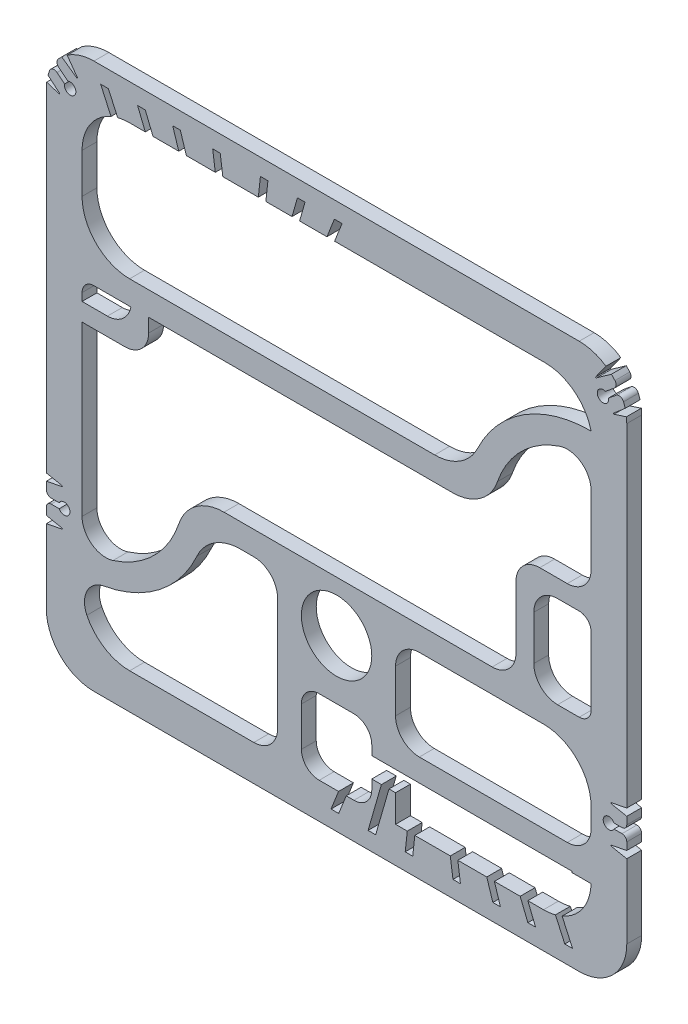
SolidWorks part; units mm, degrees
ref_plane "Front Plane" through (0, 0, 0) normal (0, 0, 1) x (1, 0, 0)
ref_plane "Top Plane" through (0, 0, 0) normal (0, 1, 0) x (1, 0, 0)
ref_plane "Right Plane" through (0, 0, 0) normal (1, 0, 0) x (0, 0, -1)
sketch "Sketch1" plane through (0, 0, 0) normal (0, 0, 1) x (1, 0, 0)
  line L0 (44.642, 21.8842) -> (44.642, 18.0742) construction
  line L1 (-10.1934, 21.8842) -> (51.7832, 21.8842)
  line L2 (-10.1934, 21.8842) -> (-10.1934, -36.406)
  line L3 (-10.1934, -36.406) -> (51.7832, -36.406)
  line L4 (51.7832, 21.8842) -> (51.7832, -36.406)
  line L5 (47.9732, -32.596) -> (-6.3834, -32.596)
  line L6 (47.9732, -32.596) -> (47.9732, 18.0742)
  line L7 (47.9732, 18.0742) -> (-6.3834, 18.0742)
  line L8 (-6.3834, -32.596) -> (-6.3834, 18.0742)
  line L9 (44.642, 19.9792) -> (-35.1587, 19.9792) construction
  line L10 (-6.3834, -31.0517) -> (-10.1934, -31.0517) construction
  line L11 (-8.2884, -31.0517) -> (-8.2884, 6.9585) construction
  line L12 (20.6521, 19.9792) -> (21.1982, 19.9792) construction
  line L14 (3.0779, -32.596) -> (3.0779, -36.406) construction
  line L15 (3.0779, -34.501) -> (37.3423, -34.501) construction
  line L16 (47.9732, -15.6937) -> (47.9732, 12.9942) construction
  line L17 (51.7832, 15.2205) -> (47.9732, 15.2205) construction
  line L18 (49.8782, 15.2205) -> (49.8782, -0.9437) construction
  line L20 (20.9378, -34.501) -> (20.3916, -34.501) construction
  line L21 (-6.3834, 8.0412) -> (-6.3834, -15.6937) construction
  dimension "D1" = 3.81
  dimension "D2" = 3.81
extrude "Boss-Extrude1" add sketch "Sketch1" along normal blind 1.5875
sketch "Sketch2" plane through (0, 0, 0) normal (0, 0, -1) x (-1, 0, 0)
  line L0 (-47.9732, -32.596) -> (-47.9732, 18.0742) construction
  line L1 (-34.8696, 3.653) -> (6.3834, 3.653)
  line L2 (-47.9732, 3.653) -> (-47.9732, 0.8076)
  line L3 (-37.4096, 1.113) -> (6.3834, 1.113)
  line L4 (6.3834, 3.653) -> (6.3834, 1.113)
  line L5 (6.3834, 18.0742) -> (6.3834, -32.596) construction
  line L6 (-33.4496, 1.113) -> (-36.4496, 1.113) construction
  line L7 (1.2504, -12.887) -> (-36.4496, -12.887) construction
  line L8 (-47.9732, -15.427) -> (-6.8239, -15.427)
  line L9 (-47.9732, -15.427) -> (-47.9732, -12.887)
  line L10 (-47.9732, -12.887) -> (-4.5259, -12.887)
  line L11 (1.357, -21.2563) -> (14.2432, -21.2563) construction
  line L12 (6.3834, -23.7963) -> (6.3834, -26.3363)
  line L13 (-47.9732, 14.2166) -> (-47.9732, 11.6766)
  arc A0 (-47.9732, 11.6766) -> (-37.4096, 1.113) centre (-47.9732, 1.113) cw
  arc A1 (-47.9732, 14.2166) -> (-34.8696, 3.653) centre (-47.9732, 0.8076) cw
  arc A2 (6.3834, -23.7963) -> (-4.5259, -12.887) centre (6.3834, -12.887) cw
  arc A3 (-6.8239, -15.427) -> (6.3834, -26.3363) centre (6.3834, -12.887) ccw
  circle A5 centre (1.357, -18.2591) radius 2.9972 construction
  line M5 (-47.9732, -32.596) -> (-47.9732, 18.0742)
  line M7 (6.3834, 18.0742) -> (6.3834, -32.596)
  dimension "D5" = 2.54
  dimension "D1" = 2.54
  dimension "D2" = 2.54
  dimension "D3" = 2.54
  dimension "D4" = 2.54
  dimension "D6" = 2.54
  dimension "D7" = 2.54
extrude "Boss-Extrude2" add sketch "Sketch2" against normal up to surface (1.5875 mm away) contours A1 A0 L3 L1 M5 M7 | L10 L8 M5 M7 region at (14.2431, 3.0939, 0) region at (-5.8234, -25.0663, 0) up to face at (20.7949, -7.2609, 1.5875)
sketch "Sketch3" plane through (0, 0, 0) normal (0, 0, -1) x (-1, 0, 0)
  line L0 (-47.9732, -1.1649) -> (-39.9496, -1.1649)
  line L1 (-47.9732, -12.887) -> (-47.9732, 11.6766) construction
  line L2 (-39.9496, -4.387) -> (-39.9496, -11.387) construction
  line L3 (-39.9496, -1.1649) -> (-39.9496, -12.887)
  line L4 (-47.9732, -12.887) -> (-4.5259, -12.887) construction
  line L5 (-39.9496, -12.887) -> (-41.8546, -12.887)
  line L6 (-41.8546, -12.887) -> (-41.8546, -3.0699)
  line L7 (-41.8546, -3.0699) -> (-47.9732, -3.0699)
  line L8 (-47.9732, -3.0699) -> (-47.9732, -1.1649)
  line L9 (-42.9468, 0.7401) -> (-53.4831, 0.7401) construction
  line L10 (-0.7296, 1.113) -> (-0.7296, -2.887)
  line L11 (-37.4096, 1.113) -> (6.3834, 1.113) construction
  line L12 (-1.9996, -2.887) -> (1.2504, -2.887) construction
  line L13 (-0.7296, -2.887) -> (6.3834, -2.887)
  line L14 (6.3834, 1.113) -> (6.3834, -23.7963) construction
  line L15 (6.3834, -2.887) -> (6.3834, -0.982)
  line L16 (6.3834, -0.982) -> (1.1754, -0.982)
  line L17 (1.1754, -0.982) -> (1.1754, 1.113)
  line L18 (1.1754, 1.113) -> (-0.7296, 1.113)
  circle A0 centre (-42.9468, 3.7373) radius 2.9972 construction
  dimension "D1" = 1.905
  dimension "D2" = 1.905
  dimension "D3" = 1.905
  dimension "D4" = 1.905
  dimension "D5" = 1.27
  dimension "D6" = 1.905
extrude "Boss-Extrude3" add sketch "Sketch3" against normal up to surface (1.5875 mm away) up to face at (20.8645, -5.9566, 1.5875)
fillet "Fillet1" radius 5.08 4 edges at (51.7832, -36.406, 0.7937) (-10.1934, -36.406, 0.7937) (-10.1934, 21.8842, 0.7937) (51.7832, 21.8842, 0.7937)
fillet "Fillet2" radius 5.08 10 edges at (6.8239, -15.427, 0.7937) (47.9732, -15.427, 0.7937) (47.9732, -32.596, 0.7937) (-6.3834, -32.596, 0.7937) (34.8696, 3.653, 0.7938) (-6.3834, 3.653, 0.7937) (47.9732, 18.0742, 0.7937) (-6.3834, 18.0742, 0.7937) (4.5259, -12.887, 0.7937) (37.4096, 1.113, 0.7938)
fillet "Fillet3" radius 2.54 10 edges at (41.8546, -3.0699, 0.7938) (39.9496, -12.887, 0.7938) (41.8546, -12.887, 0.7938) (39.9496, -1.1649, 0.7938) (47.9732, -1.1649, 0.7938) (-1.1754, -0.982, 0.7938) (0.7296, -2.887, 0.7938) (47.9732, 11.6766, 0.7937) (-6.3834, -26.3363, 0.7937) (-6.3834, -23.7963, 0.7937)
fillet "Fillet4" radius 1.27 3 edges at (47.9732, -12.887, 0.7937) (47.9732, -3.0699, 0.7938) (-6.3834, 1.113, 0.7938)
sketch "Sketch5" plane through (0, 0, 0) normal (0, 0, -1) x (-1, 0, 0)
  line L0 (-42.8932, -15.427) -> (-10.5066, -15.427) construction
  line L1 (-27.0941, -15.427) -> (-14.4957, -15.427)
  line L2 (-27.0941, -15.427) -> (-27.0941, -32.596)
  line L3 (-27.0941, -32.596) -> (-14.4957, -32.596)
  line L4 (-14.4957, -15.427) -> (-14.4957, -32.596)
  line L5 (1.3034, -32.596) -> (-42.8932, -32.596) construction
  line L6 (-24.5541, -18.2972) -> (-27.0941, -18.2972) construction
  line L9 (-17.0357, -18.2972) -> (-14.4957, -18.2972) construction
  circle A1 centre (-20.7949, -18.2972) radius 3.7592 construction
  dimension "D1" = 2.54
extrude "Boss-Extrude4" add sketch "Sketch5" against normal up to surface (1.5875 mm away) up to face at (-4.5227, -0.0173, 1.5875)
sketch "Sketch6" plane through (0, 0, 0) normal (0, 0, -1) x (-1, 0, 0)
  circle A0 centre (-20.7949, -18.2972) radius 3.7592 construction
  circle A1 centre (-20.7949, -18.2972) radius 3.7592
extrude "Cut-Extrude2" cut sketch "Sketch6" against normal up to surface (1.5875 mm away) up to face at (4.768, -24.4396, 1.5875)
sketch "Sketch7" plane through (0, 0, 0) normal (0, 0, -1) x (-1, 0, 0)
  line L0 (-27.0941, -15.427) -> (-27.0941, -32.596) construction
  line L1 (-24.5541, -24.5964) -> (-17.0357, -24.5964)
  line L2 (-24.5541, -24.5964) -> (-24.5541, -32.596)
  line L3 (-24.5541, -32.596) -> (-17.0357, -32.596)
  line L4 (-17.0357, -24.5964) -> (-17.0357, -32.596)
  line L5 (-14.4957, -32.596) -> (-14.4957, -15.427) construction
  line L6 (1.3034, -32.596) -> (-14.4957, -32.596) construction
  line L7 (-20.7949, -22.0564) -> (-6.5424, -22.0564) construction
  line L8 (-20.7949, -22.0564) -> (-20.7949, -21.3452) construction
  circle A0 centre (-20.7949, -18.2972) radius 3.7592 construction
  dimension "D1" = 2.54
  dimension "D2" = 2.54
  dimension "D3" = 2.54
extrude "Cut-Extrude3" cut sketch "Sketch7" against normal up to surface (1.5875 mm away) up to face at (24.5541, -18.2972, 1.5875)
fillet "Fillet5" radius 1.905 4 edges at (24.5541, -32.596, 0.7937) (17.0357, -32.596, 0.7938) (17.0357, -24.5964, 0.7938) (24.5541, -24.5964, 0.7938)
sketch "Sketch8" plane through (0, 0, 0) normal (0, 0, -1) x (-1, 0, 0)
  line L0 (-47.9732, -27.516) -> (-47.9732, -20.507) construction
  line L1 (-47.9732, -25.103) -> (-27.0941, -25.103)
  line L2 (-47.9732, -25.103) -> (-47.9732, -27.643)
  line L3 (-47.9732, -27.643) -> (-27.0941, -27.643)
  line L4 (-27.0941, -25.103) -> (-27.0941, -27.643)
  line L5 (-27.0941, -15.427) -> (-27.0941, -32.596) construction
  line L6 (-45.7916, -27.643) -> (-20.3916, -27.643) construction
  dimension "D1" = 2.54
extrude "Boss-Extrude5" add sketch "Sketch8" against normal up to surface (1.5875 mm away) up to face at (20.7949, -28.5962, 1.5875)
fillet "Fillet6" radius 2.54 5 edges at (27.0941, -15.427, 0.7937) (14.4957, -15.427, 0.7937) (14.4957, -32.596, 0.7937) (27.0941, -25.103, 0.7937) (47.9732, -25.103, 0.7937)
sketch "Sketch4" plane through (0, 0, 0) normal (0, 0, -1) x (-1, 0, 0)
  line L0 (3.2504, -2.887) -> (4.7504, -4.387) construction
  line L1 (4.7504, -11.387) -> (3.2504, -12.887) construction
  line L2 (3.2504, -2.887) -> (4.7504, -4.387)
  line L3 (4.7504, -11.387) -> (3.2504, -12.887)
  line L4 (4.7504, -4.387) -> (4.7504, -11.387) construction
  line L5 (4.7504, -4.387) -> (4.7504, -11.387)
  line L6 (3.2504, -2.887) -> (3.2504, -12.887)
  line L32 (4.2018, 13.1212) -> (4.2018, 15.0262)
  line L33 (4.2018, 15.0262) -> (1.9539, 15.0262)
  line L34 (1.9539, 15.0262) -> (4.2018, 19.9792)
  line L35 (4.2018, 19.9792) -> (3.6556, 19.9792)
  line L36 (3.6556, 19.9792) -> (1.4078, 15.0262)
  line L37 (1.4078, 15.0262) -> (-1.7417, 15.0262)
  line L38 (-1.7417, 15.0262) -> (0.2648, 19.9792)
  line L39 (0.2648, 19.9792) -> (-0.2814, 19.9792)
  line L40 (-0.2814, 19.9792) -> (-2.2879, 15.0262)
  line L41 (-2.2879, 15.0262) -> (-5.0437, 15.0262)
  line L42 (-5.0437, 15.0262) -> (-3.469, 19.9792)
  line L43 (-3.469, 19.9792) -> (-4.0152, 19.9792)
  line L44 (-4.0152, 19.9792) -> (-5.5899, 15.0262)
  line L45 (-5.5899, 15.0262) -> (-8.3965, 15.0262)
  line L46 (-8.3965, 15.0262) -> (-7.7108, 19.9792)
  line L47 (-7.7108, 19.9792) -> (-8.257, 19.9792)
  line L48 (-8.257, 19.9792) -> (-8.9427, 15.0262)
  line L49 (-8.9427, 15.0262) -> (-12.2319, 15.0262)
  line L50 (-12.2319, 15.0262) -> (-12.7781, 19.9792)
  line L51 (-12.7781, 19.9792) -> (-13.3242, 19.9792)
  line L52 (-13.3242, 19.9792) -> (-12.7781, 15.0262)
  line L53 (-12.7781, 15.0262) -> (-15.2926, 15.0262)
  line L54 (-15.2926, 15.0262) -> (-16.7151, 19.9792)
  line L55 (-16.7151, 19.9792) -> (-17.2612, 19.9792)
  line L56 (-17.2612, 19.9792) -> (-15.8388, 15.0262)
  line L57 (-15.8388, 15.0262) -> (-18.6963, 15.0262)
  line L58 (-18.6963, 15.0262) -> (-20.6521, 19.9792)
  line L59 (-20.6521, 19.9792) -> (-21.1982, 19.9792)
  line L60 (-21.1982, 19.9792) -> (-19.2425, 15.0262)
  line L61 (-19.2425, 15.0262) -> (-21.1982, 15.0262)
  line L62 (-21.1982, 15.0262) -> (-21.1982, 13.1212)
  line L63 (-21.1982, 13.1212) -> (4.2018, 13.1212)
  line L64 (4.2018, 13.1212) -> (4.2018, 15.0262) construction
  line L65 (4.2018, 15.0262) -> (1.9539, 15.0262) construction
  line L66 (1.9539, 15.0262) -> (4.2018, 19.9792) construction
  line L67 (4.2018, 19.9792) -> (3.6556, 19.9792) construction
  line L68 (3.6556, 19.9792) -> (1.4078, 15.0262) construction
  line L69 (1.4078, 15.0262) -> (-1.7417, 15.0262) construction
  line L70 (-1.7417, 15.0262) -> (0.2648, 19.9792) construction
  line L71 (0.2648, 19.9792) -> (-0.2814, 19.9792) construction
  line L72 (-0.2814, 19.9792) -> (-2.2879, 15.0262) construction
  line L73 (-2.2879, 15.0262) -> (-5.0437, 15.0262) construction
  line L74 (-5.0437, 15.0262) -> (-3.469, 19.9792) construction
  line L75 (-3.469, 19.9792) -> (-4.0152, 19.9792) construction
  line L76 (-4.0152, 19.9792) -> (-5.5899, 15.0262) construction
  line L77 (-5.5899, 15.0262) -> (-8.3965, 15.0262) construction
  line L78 (-8.3965, 15.0262) -> (-7.7108, 19.9792) construction
  line L79 (-7.7108, 19.9792) -> (-8.257, 19.9792) construction
  line L80 (-8.257, 19.9792) -> (-8.9427, 15.0262) construction
  line L81 (-8.9427, 15.0262) -> (-12.2319, 15.0262) construction
  line L82 (-12.2319, 15.0262) -> (-12.7781, 19.9792) construction
  line L83 (-12.7781, 19.9792) -> (-13.3242, 19.9792) construction
  line L84 (-13.3242, 19.9792) -> (-12.7781, 15.0262) construction
  line L85 (-12.7781, 15.0262) -> (-15.2926, 15.0262) construction
  line L86 (-15.2926, 15.0262) -> (-16.7151, 19.9792) construction
  line L87 (-16.7151, 19.9792) -> (-17.2612, 19.9792) construction
  line L88 (-17.2612, 19.9792) -> (-15.8388, 15.0262) construction
  line L89 (-15.8388, 15.0262) -> (-18.6963, 15.0262) construction
  line L90 (-18.6963, 15.0262) -> (-20.6521, 19.9792) construction
  line L91 (-20.6521, 19.9792) -> (-21.1982, 19.9792) construction
  line L92 (-21.1982, 19.9792) -> (-19.2425, 15.0262) construction
  line L93 (-19.2425, 15.0262) -> (-21.1982, 15.0262) construction
  line L94 (-21.1982, 15.0262) -> (-21.1982, 13.1212) construction
  line L95 (-21.1982, 13.1212) -> (4.2018, 13.1212) construction
  line L96 (-45.7916, -27.643) -> (-45.7916, -29.548)
  line L97 (-45.7916, -29.548) -> (-43.5438, -29.548)
  line L98 (-43.5438, -29.548) -> (-45.7916, -34.501)
  line L99 (-45.7916, -34.501) -> (-45.2455, -34.501)
  line L100 (-45.2455, -34.501) -> (-42.9976, -29.548)
  line L101 (-42.9976, -29.548) -> (-39.8482, -29.548)
  line L102 (-39.8482, -29.548) -> (-41.8546, -34.501)
  line L103 (-41.8546, -34.501) -> (-41.3085, -34.501)
  line L104 (-41.3085, -34.501) -> (-39.302, -29.548)
  line L105 (-39.302, -29.548) -> (-36.5462, -29.548)
  line L106 (-36.5462, -29.548) -> (-38.1208, -34.501)
  line L107 (-38.1208, -34.501) -> (-37.5747, -34.501)
  line L108 (-37.5747, -34.501) -> (-36, -29.548)
  line L109 (-36, -29.548) -> (-33.1934, -29.548)
  line L110 (-33.1934, -29.548) -> (-33.879, -34.501)
  line L111 (-33.879, -34.501) -> (-33.3329, -34.501)
  line L112 (-33.3329, -34.501) -> (-32.6472, -29.548)
  line L113 (-32.6472, -29.548) -> (-29.358, -29.548)
  line L114 (-29.358, -29.548) -> (-28.8118, -34.501)
  line L115 (-28.8118, -34.501) -> (-28.2656, -34.501)
  line L116 (-28.2656, -34.501) -> (-28.8118, -29.548)
  line L117 (-28.8118, -29.548) -> (-26.2973, -29.548)
  line L118 (-26.2973, -29.548) -> (-24.8748, -34.501)
  line L119 (-24.8748, -34.501) -> (-24.3286, -34.501)
  line L120 (-24.3286, -34.501) -> (-25.7511, -29.548)
  line L121 (-25.7511, -29.548) -> (-22.8935, -29.548)
  line L122 (-22.8935, -29.548) -> (-20.9378, -34.501)
  line L123 (-20.9378, -34.501) -> (-20.3916, -34.501)
  line L124 (-20.3916, -34.501) -> (-22.3474, -29.548)
  line L125 (-22.3474, -29.548) -> (-20.3916, -29.548)
  line L126 (-20.3916, -29.548) -> (-20.3916, -27.643)
  line L127 (-20.3916, -27.643) -> (-45.7916, -27.643)
  line L128 (-45.7916, -27.643) -> (-45.7916, -29.548) construction
  line L129 (-45.7916, -29.548) -> (-43.5438, -29.548) construction
  line L130 (-43.5438, -29.548) -> (-45.7916, -34.501) construction
  line L131 (-45.7916, -34.501) -> (-45.2455, -34.501) construction
  line L132 (-45.2455, -34.501) -> (-42.9976, -29.548) construction
  line L133 (-42.9976, -29.548) -> (-39.8482, -29.548) construction
  line L134 (-39.8482, -29.548) -> (-41.8546, -34.501) construction
  line L135 (-41.8546, -34.501) -> (-41.3085, -34.501) construction
  line L136 (-41.3085, -34.501) -> (-39.302, -29.548) construction
  line L137 (-39.302, -29.548) -> (-36.5462, -29.548) construction
  line L138 (-36.5462, -29.548) -> (-38.1208, -34.501) construction
  line L139 (-38.1208, -34.501) -> (-37.5747, -34.501) construction
  line L140 (-37.5747, -34.501) -> (-36, -29.548) construction
  line L141 (-36, -29.548) -> (-33.1934, -29.548) construction
  line L142 (-33.1934, -29.548) -> (-33.879, -34.501) construction
  line L143 (-33.879, -34.501) -> (-33.3329, -34.501) construction
  line L144 (-33.3329, -34.501) -> (-32.6472, -29.548) construction
  line L145 (-32.6472, -29.548) -> (-29.358, -29.548) construction
  line L146 (-29.358, -29.548) -> (-28.8118, -34.501) construction
  line L147 (-28.8118, -34.501) -> (-28.2656, -34.501) construction
  line L148 (-28.2656, -34.501) -> (-28.8118, -29.548) construction
  line L149 (-28.8118, -29.548) -> (-26.2973, -29.548) construction
  line L150 (-26.2973, -29.548) -> (-24.8748, -34.501) construction
  line L151 (-24.8748, -34.501) -> (-24.3286, -34.501) construction
  line L152 (-24.3286, -34.501) -> (-25.7511, -29.548) construction
  line L153 (-25.7511, -29.548) -> (-22.8935, -29.548) construction
  line L154 (-22.8935, -29.548) -> (-20.9378, -34.501) construction
  line L155 (-20.9378, -34.501) -> (-20.3916, -34.501) construction
  line L156 (-20.3916, -34.501) -> (-22.3474, -29.548) construction
  line L157 (-22.3474, -29.548) -> (-20.3916, -29.548) construction
  line L158 (-20.3916, -29.548) -> (-20.3916, -27.643) construction
  line L159 (-20.3916, -27.643) -> (-45.7916, -27.643) construction
  line L263 (4.3288, 12.9942) -> (4.3288, 15.1532)
  line L264 (4.3288, 15.1532) -> (2.151, 15.1532)
  line L265 (2.151, 15.1532) -> (4.3989, 20.1062)
  line L266 (4.3989, 20.1062) -> (3.5738, 20.1062)
  line L267 (3.5738, 20.1062) -> (1.3259, 15.1532)
  line L268 (1.3259, 15.1532) -> (-1.5532, 15.1532)
  line L269 (-1.5532, 15.1532) -> (0.4532, 20.1062)
  line L270 (0.4532, 20.1062) -> (-0.367, 20.1062)
  line L271 (-0.367, 20.1062) -> (-2.3735, 15.1532)
  line L272 (-2.3735, 15.1532) -> (-4.8701, 15.1532)
  line L273 (-4.8701, 15.1532) -> (-3.2954, 20.1062)
  line L274 (-3.2954, 20.1062) -> (-4.1081, 20.1062)
  line L275 (-4.1081, 20.1062) -> (-5.6828, 15.1532)
  line L276 (-5.6828, 15.1532) -> (-8.2507, 15.1532)
  line L277 (-8.2507, 15.1532) -> (-7.565, 20.1062)
  line L278 (-7.565, 20.1062) -> (-8.3676, 20.1062)
  line L279 (-8.3676, 20.1062) -> (-9.0533, 15.1532)
  line L280 (-9.0533, 15.1532) -> (-12.1181, 15.1532)
  line L281 (-12.1181, 15.1532) -> (-12.6643, 20.1062)
  line L282 (-12.6643, 20.1062) -> (-13.466, 20.1062)
  line L283 (-13.466, 20.1062) -> (-12.9198, 15.1532)
  line L284 (-12.9198, 15.1532) -> (-15.1969, 15.1532)
  line L285 (-15.1969, 15.1532) -> (-16.6194, 20.1062)
  line L286 (-16.6194, 20.1062) -> (-17.4298, 20.1062)
  line L287 (-17.4298, 20.1062) -> (-16.0074, 15.1532)
  line L288 (-16.0074, 15.1532) -> (-18.6099, 15.1532)
  line L289 (-18.6099, 15.1532) -> (-20.5657, 20.1062)
  line L290 (-20.5657, 20.1062) -> (-21.3849, 20.1062)
  line L291 (-21.3849, 20.1062) -> (-19.4292, 15.1532)
  line L292 (-19.4292, 15.1532) -> (-21.3252, 15.1532)
  line L293 (-21.3252, 15.1532) -> (-21.3252, 12.9942)
  line L294 (-21.3252, 12.9942) -> (4.3288, 12.9942)
  line L295 (-45.9186, -27.516) -> (-45.9186, -29.675)
  line L296 (-45.9186, -29.675) -> (-43.7409, -29.675)
  line L297 (-43.7409, -29.675) -> (-45.9887, -34.628)
  line L298 (-45.9887, -34.628) -> (-45.1636, -34.628)
  line L299 (-45.1636, -34.628) -> (-42.9158, -29.675)
  line L300 (-42.9158, -29.675) -> (-40.0367, -29.675)
  line L301 (-40.0367, -29.675) -> (-42.0431, -34.628)
  line L302 (-42.0431, -34.628) -> (-41.2229, -34.628)
  line L303 (-41.2229, -34.628) -> (-39.2164, -29.675)
  line L304 (-39.2164, -29.675) -> (-36.7198, -29.675)
  line L305 (-36.7198, -29.675) -> (-38.2945, -34.628)
  line L306 (-38.2945, -34.628) -> (-37.4818, -34.628)
  line L307 (-37.4818, -34.628) -> (-35.9071, -29.675)
  line L308 (-35.9071, -29.675) -> (-33.3392, -29.675)
  line L309 (-33.3392, -29.675) -> (-34.0248, -34.628)
  line L310 (-34.0248, -34.628) -> (-33.2222, -34.628)
  line L311 (-33.2222, -34.628) -> (-32.5366, -29.675)
  line L312 (-32.5366, -29.675) -> (-29.4717, -29.675)
  line L313 (-29.4717, -29.675) -> (-28.9256, -34.628)
  line L314 (-28.9256, -34.628) -> (-28.1239, -34.628)
  line L315 (-28.1239, -34.628) -> (-28.67, -29.675)
  line L316 (-28.67, -29.675) -> (-26.3929, -29.675)
  line L317 (-26.3929, -29.675) -> (-24.9705, -34.628)
  line L318 (-24.9705, -34.628) -> (-24.16, -34.628)
  line L319 (-24.16, -34.628) -> (-25.5825, -29.675)
  line L320 (-25.5825, -29.675) -> (-22.9799, -29.675)
  line L321 (-22.9799, -29.675) -> (-21.0242, -34.628)
  line L322 (-21.0242, -34.628) -> (-20.205, -34.628)
  line L323 (-20.205, -34.628) -> (-22.1607, -29.675)
  line L324 (-22.1607, -29.675) -> (-20.2646, -29.675)
  line L325 (-20.2646, -29.675) -> (-20.2646, -27.516)
  line L326 (-20.2646, -27.516) -> (-45.9186, -27.516)
  dimension "D1" = 0
  dimension "D2" = 0
  dimension "D3" = 0.127
  dimension "D4" = 0.127
extrude "Cut-Extrude1" cut sketch "Sketch4" against normal up to surface (1.5875 mm away) up to face at (37.2819, -20.5167, 1.5875)
sketch "Sketch9" plane through (0, 0, 0) normal (0, 0, -1) x (-1, 0, 0)
  circle A0 centre (-49.2432, 18.0742) radius 0.6096 construction
  circle A1 centre (7.6534, 18.0742) radius 0.6096 construction
  circle A2 centre (8.2884, -21.0912) radius 0.6096 construction
  circle A3 centre (-49.8782, -21.0912) radius 0.6096 construction
  circle A4 centre (-49.2432, 18.0742) radius 0.6096
  circle A5 centre (7.6534, 18.0742) radius 0.6096
  circle A6 centre (8.2884, -21.0912) radius 0.6096
  circle A7 centre (-49.8782, -21.0912) radius 0.6096
extrude "Cut-Extrude4" cut sketch "Sketch9" against normal up to surface (1.5875 mm away) up to face at (31.4097, -31.792, 1.5875)
sketch "Sketch10" plane through (0, 0, 1.5875) normal (0, 0, 1) x (1, 0, 0)
  line L0 (-6.8849, 19.4812) -> (-7.9722, 21.0034) construction
  line L1 (-8.5477, 20.5474) -> (-6.9558, 19.4104) construction
  line L2 (-7.8965, 18.6332) -> (-8.8699, 19.4273) construction
  line L3 (-9.0531, 18.8556) -> (-8.2498, 18.2002) construction
  line L4 (-8.7923, 17.0799) -> (-10.0187, 18.1248) construction
  line L5 (-10.1564, 17.4156) -> (-8.8408, 16.9929) construction
  line L6 (-6.8849, 19.4812) -> (-7.9722, 21.0034)
  line L7 (-8.5477, 20.5474) -> (-6.9558, 19.4104)
  line L8 (-7.8965, 18.6332) -> (-8.8699, 19.4273)
  line L9 (-9.0531, 18.8556) -> (-8.2498, 18.2002)
  line L10 (-8.7923, 17.0799) -> (-10.0187, 18.1248)
  line L11 (-10.1564, 17.4156) -> (-8.8408, 16.9929)
  line L12 (48.4748, 19.4812) -> (49.5621, 21.0034) construction
  line L13 (50.1376, 20.5474) -> (48.5457, 19.4104) construction
  line L14 (49.4864, 18.6332) -> (50.4598, 19.4273) construction
  line L15 (50.643, 18.8556) -> (49.8397, 18.2002) construction
  line L16 (50.3822, 17.0799) -> (51.6086, 18.1248) construction
  line L17 (51.7463, 17.4156) -> (50.4306, 16.9929) construction
  line L18 (50.1273, -19.0774) -> (51.7832, -18.7463) construction
  line L19 (51.7832, -19.5083) -> (50.1273, -19.1771) construction
  line L21 (50.42, -20.8118) -> (51.2752, -20.8118) construction
  line L22 (51.2752, -21.3706) -> (50.42, -21.3706) construction
  line L24 (50.1273, -23.0053) -> (51.7832, -22.6741) construction
  line L25 (51.7832, -23.4361) -> (50.1273, -23.105) construction
  line L26 (-8.5374, -19.0774) -> (-10.1934, -18.7463) construction
  line L27 (-10.1934, -19.5083) -> (-8.5374, -19.1771) construction
  line L29 (-8.8302, -20.8118) -> (-9.6854, -20.8118) construction
  line L30 (-9.6854, -21.3706) -> (-8.8302, -21.3706) construction
  line L32 (-8.5374, -23.0053) -> (-10.1934, -22.6741) construction
  line L33 (-10.1934, -23.4361) -> (-8.5374, -23.105) construction
  line L34 (48.4748, 19.4812) -> (49.5621, 21.0034)
  line L35 (50.1376, 20.5474) -> (48.5457, 19.4104)
  line L36 (49.4864, 18.6332) -> (50.4598, 19.4273)
  line L37 (50.643, 18.8556) -> (49.8397, 18.2002)
  line L38 (50.3822, 17.0799) -> (51.6086, 18.1248)
  line L39 (51.7463, 17.4156) -> (50.4306, 16.9929)
  line L40 (50.1273, -19.0774) -> (51.7832, -18.7463)
  line L41 (51.7832, -19.5083) -> (50.1273, -19.1771)
  line L42 (51.7832, -31.326) -> (51.7832, 16.8042) construction
  line L43 (50.42, -20.8118) -> (51.2752, -20.8118)
  line L44 (51.2752, -21.3706) -> (50.42, -21.3706)
  line L45 (51.7832, -23.4361) -> (51.7832, -22.6741)
  line L46 (50.1273, -23.0053) -> (51.7832, -22.6741)
  line L47 (51.7832, -23.4361) -> (50.1273, -23.105)
  line L48 (-8.5374, -19.0774) -> (-10.1934, -18.7463)
  line L49 (-10.1934, -19.5083) -> (-8.5374, -19.1771)
  line L50 (-10.1934, -20.3038) -> (-10.1934, -21.8786)
  line L51 (-8.8302, -20.8118) -> (-9.6854, -20.8118)
  line L52 (-9.6854, -21.3706) -> (-8.8302, -21.3706)
  line L53 (51.7832, -19.5083) -> (51.7832, -18.7463)
  line L54 (-8.5374, -23.0053) -> (-10.1934, -22.6741)
  line L55 (-10.1934, -23.4361) -> (-8.5374, -23.105)
  line L56 (-10.1934, 16.8042) -> (-10.1934, -31.326) construction
  line L57 (-10.1934, -18.7463) -> (-10.1934, -19.5083)
  line L58 (-10.1934, -22.6741) -> (-10.1934, -23.4361)
  line L59 (51.7832, -21.8786) -> (51.7832, -20.3038)
  arc A0 (-6.9558, 19.4104) -> (-6.8849, 19.4812) centre (-6.9263, 19.4517) ccw construction
  arc A1 (-8.9305, 20.1561) -> (-8.8699, 19.4273) centre (-8.5488, 19.821) ccw construction
  arc A2 (-9.0531, 18.8556) -> (-9.8477, 18.6461) centre (-9.3742, 18.462) ccw construction
  arc A4 (-8.8408, 16.9929) -> (-8.7923, 17.0799) centre (-8.8252, 17.0412) ccw construction
  arc A5 (-6.9558, 19.4104) -> (-6.8849, 19.4812) centre (-6.9263, 19.4517) ccw
  arc A6 (-8.9305, 20.1561) -> (-8.8699, 19.4273) centre (-8.5488, 19.821) ccw
  arc A7 (-9.0531, 18.8556) -> (-9.8477, 18.6461) centre (-9.3742, 18.462) ccw
  arc A8 (-10.0187, 18.1248) -> (-10.1564, 17.4156) centre (-5.1134, 16.8042) ccw
  arc A9 (-8.8408, 16.9929) -> (-8.7923, 17.0799) centre (-8.8252, 17.0412) ccw
  arc A10 (-5.1134, 21.8842) -> (-10.1934, 16.8042) centre (-5.1134, 16.8042) ccw construction
  circle A11 centre (-7.6534, 18.0742) radius 0.6096 construction
  arc A12 (-7.9722, 21.0034) -> (-8.5477, 20.5474) centre (-5.1134, 16.8042) ccw
  arc A13 (-7.8965, 18.6332) -> (-8.2498, 18.2002) centre (-7.6534, 18.0742) ccw
  arc A14 (-8.9305, 20.1561) -> (-9.8477, 18.6461) centre (-5.1134, 16.8042) ccw
  arc A15 (48.4748, 19.4812) -> (48.5457, 19.4104) centre (48.5162, 19.4517) ccw construction
  arc A17 (50.4598, 19.4273) -> (50.5204, 20.1561) centre (50.1387, 19.821) ccw construction
  arc A18 (51.4375, 18.6461) -> (50.643, 18.8556) centre (50.9641, 18.462) ccw construction
  arc A20 (50.3822, 17.0799) -> (50.4306, 16.9929) centre (50.4151, 17.0412) ccw construction
  arc A21 (50.1273, -19.0774) -> (50.1273, -19.1771) centre (50.1373, -19.1273) ccw construction
  arc A22 (51.2752, -20.8118) -> (51.7832, -20.3038) centre (51.2752, -20.3038) ccw construction
  arc A23 (51.7832, -21.8786) -> (51.2752, -21.3706) centre (51.2752, -21.8786) ccw construction
  arc A24 (50.1273, -23.0053) -> (50.1273, -23.105) centre (50.1373, -23.0551) ccw construction
  arc A25 (-8.5374, -19.1771) -> (-8.5374, -19.0774) centre (-8.5474, -19.1273) ccw construction
  arc A26 (-10.1934, -20.3038) -> (-9.6854, -20.8118) centre (-9.6854, -20.3038) ccw construction
  arc A27 (-9.6854, -21.3706) -> (-10.1934, -21.8786) centre (-9.6854, -21.8786) ccw construction
  arc A28 (-8.5374, -23.105) -> (-8.5374, -23.0053) centre (-8.5474, -23.0551) ccw construction
  arc A29 (48.4748, 19.4812) -> (48.5457, 19.4104) centre (48.5162, 19.4517) ccw
  arc A30 (50.1376, 20.5474) -> (49.5621, 21.0034) centre (46.7032, 16.8042) ccw
  arc A31 (50.4598, 19.4273) -> (50.5204, 20.1561) centre (50.1387, 19.821) ccw
  arc A32 (51.4375, 18.6461) -> (50.643, 18.8556) centre (50.9641, 18.462) ccw
  arc A33 (51.4375, 18.6461) -> (50.5204, 20.1561) centre (46.7032, 16.8042) ccw
  arc A34 (50.3822, 17.0799) -> (50.4306, 16.9929) centre (50.4151, 17.0412) ccw
  arc A35 (50.1273, -19.0774) -> (50.1273, -19.1771) centre (50.1373, -19.1273) ccw
  arc A36 (51.2752, -20.8118) -> (51.7832, -20.3038) centre (51.2752, -20.3038) ccw
  arc A37 (51.7832, -21.8786) -> (51.2752, -21.3706) centre (51.2752, -21.8786) ccw
  arc A38 (50.1273, -23.0053) -> (50.1273, -23.105) centre (50.1373, -23.0551) ccw
  arc A39 (-8.5374, -19.1771) -> (-8.5374, -19.0774) centre (-8.5474, -19.1273) ccw
  arc A40 (-10.1934, -20.3038) -> (-9.6854, -20.8118) centre (-9.6854, -20.3038) ccw
  arc A41 (-9.6854, -21.3706) -> (-10.1934, -21.8786) centre (-9.6854, -21.8786) ccw
  arc A42 (-8.5374, -23.105) -> (-8.5374, -23.0053) centre (-8.5474, -23.0551) ccw
  circle A43 centre (-8.2884, -21.0912) radius 0.6096 construction
  arc A44 (-8.8302, -20.8118) -> (-8.8302, -21.3706) centre (-8.2884, -21.0912) ccw
  circle A45 centre (49.8782, -21.0912) radius 0.6096 construction
  arc A46 (50.42, -21.3706) -> (50.42, -20.8118) centre (49.8782, -21.0912) ccw
  circle A47 centre (49.2432, 18.0742) radius 0.6096 construction
  arc A48 (51.7832, 16.8042) -> (46.7032, 21.8842) centre (46.7032, 16.8042) ccw construction
  arc A49 (49.8397, 18.2002) -> (49.4864, 18.6332) centre (49.2432, 18.0742) ccw
  arc A50 (51.7463, 17.4156) -> (51.6086, 18.1248) centre (46.7032, 16.8042) ccw
extrude "Slots for carbon" cut sketch "Sketch10" against normal through all
